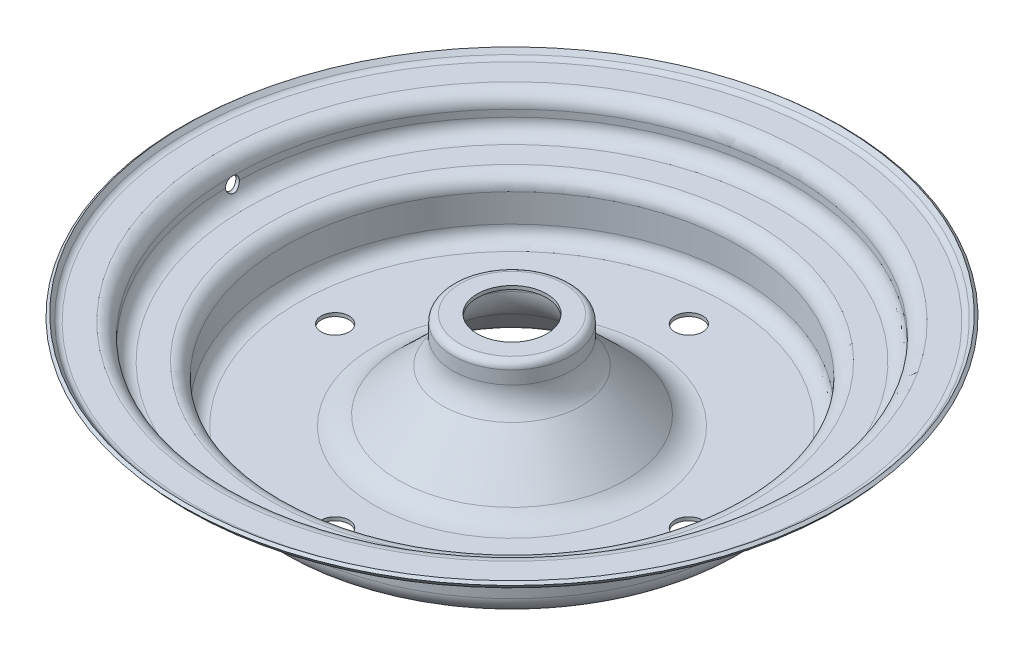
SolidWorks part; units mm, degrees
ref_plane "Ön Düzlem" through (0, 0, 0) normal (0, 0, 1) x (1, 0, 0)
ref_plane "Üst Düzlem" through (0, 0, 0) normal (0, 1, 0) x (1, 0, 0)
ref_plane "Sağ Düzlem" through (0, 0, 0) normal (1, 0, 0) x (0, 0, -1)
sketch "Çizim1" plane through (0, 0, 0) normal (0, 0, 1) x (1, 0, 0)
  line L0 (0, 39.6036) -> (0, -43.2542) construction
  line L1 (-94.234, 34.6808) -> (-93.2265, 33.4801)
  line L2 (-91.6944, 32.7656) -> (-84.627, 32.7656)
  line L3 (-80.627, 28.7656) -> (-80.627, 26.7656)
  line L4 (-76.627, 22.7656) -> (-69.627, 22.7656)
  line L5 (-65.627, 18.7656) -> (-65.627, 10.6808)
  line L6 (-61.627, 6.6808) -> (-39.6692, 6.6808)
  line L7 (-32.7202, 9.4897) -> (-20.051, 21.7325)
  line L8 (-17, 28.9235) -> (-17, 32.6808)
  line L9 (0, 0) -> (-159.2836, 0) construction
  line L10 (-15, 34.6808) -> (-10, 34.6808)
  line L11 (-95, 34.038) -> (-93.9925, 32.8373)
  line L12 (-91.6944, 31.7656) -> (-84.627, 31.7656)
  line L13 (-81.627, 28.7656) -> (-81.627, 26.7656)
  line L14 (-76.627, 21.7656) -> (-69.627, 21.7656)
  line L15 (-66.627, 18.7656) -> (-66.627, 10.6808)
  line L16 (-61.627, 5.6808) -> (-39.6692, 5.6808)
  line L17 (-32.0253, 8.7706) -> (-19.3561, 21.0134)
  line L18 (-16, 28.9235) -> (-16, 32.6808)
  line L19 (-15, 33.6808) -> (-11, 33.6808)
  line L20 (-94.234, 34.6808) -> (-95, 34.038)
  line L26 (-15, 33.6808) -> (-10, 33.6808) construction
  line L28 (-11, 33.6808) -> (-10, 33.6808)
  line L29 (-10, 33.6808) -> (-10, 34.6808)
  arc A0 (-65.627, 10.6808) -> (-61.627, 6.6808) centre (-61.627, 10.6808) ccw
  arc A1 (-69.627, 22.7656) -> (-65.627, 18.7656) centre (-69.627, 18.7656) cw
  arc A2 (-80.627, 26.7656) -> (-76.627, 22.7656) centre (-76.627, 26.7656) ccw
  arc A3 (-84.627, 32.7656) -> (-80.627, 28.7656) centre (-84.627, 28.7656) cw
  arc A4 (-39.6692, 6.6808) -> (-32.7202, 9.4897) centre (-39.6692, 16.6808) ccw
  arc A5 (-20.051, 21.7325) -> (-17, 28.9235) centre (-27, 28.9235) ccw
  arc A6 (-17, 32.6808) -> (-15, 34.6808) centre (-15, 32.6808) cw
  arc A7 (-93.2265, 33.4801) -> (-91.6944, 32.7656) centre (-91.6944, 34.7656) ccw
  arc A8 (-93.9925, 32.8373) -> (-91.6944, 31.7656) centre (-91.6944, 34.7656) ccw
  arc A9 (-84.627, 31.7656) -> (-81.627, 28.7656) centre (-84.627, 28.7656) cw
  arc A10 (-81.627, 26.7656) -> (-76.627, 21.7656) centre (-76.627, 26.7656) ccw
  arc A11 (-69.627, 21.7656) -> (-66.627, 18.7656) centre (-69.627, 18.7656) cw
  arc A12 (-66.627, 10.6808) -> (-61.627, 5.6808) centre (-61.627, 10.6808) ccw
  arc A13 (-39.6692, 5.6808) -> (-32.0253, 8.7706) centre (-39.6692, 16.6808) ccw
  arc A14 (-19.3561, 21.0134) -> (-16, 28.9235) centre (-27, 28.9235) ccw
  arc A15 (-16, 32.6808) -> (-15, 33.6808) centre (-15, 32.6808) cw
  point P30 (-65.627, 6.6808)
  point P33 (-65.627, 22.7656)
  point P36 (-80.627, 22.7656)
  point P39 (-80.627, 32.7656)
  point P42 (-35.627, 6.6808)
  point P45 (-17, 24.6808)
  point P48 (-17, 34.6808)
  point P51 (-92.627, 32.7656)
  dimension "D13" = 4
  dimension "D14" = 10
  dimension "D15" = 10
  dimension "D16" = 2
  dimension "D17" = 2
  dimension "D2" = 10
  dimension "D3" = 10
  dimension "D4" = 28
  dimension "D5" = 95
  dimension "D6" = 28
  dimension "D7" = 2.5
  dimension "D8" = 12
  dimension "D9" = 10
  dimension "D10" = 30
  dimension "D11" = 15
  dimension "D12" = 50
  dimension "D19" = 16
  dimension "D18" = 1
revolve "Döndür1" add sketch "Çizim1" angle 360 about L0 other way angle 360
sketch "Çizim2" plane through (0, 6.6808, 0) normal (0, 1, 0) x (1, 0, 0)
  circle A7 centre (0, 50.9725) radius 4
  circle A8 centre (50.9725, 0) radius 4
  circle A9 centre (0, -50.9725) radius 4
  circle A10 centre (-50.9725, 0) radius 4
  dimension "D2" = 8
  dimension "D3" = 8
  dimension "D4" = 8
  dimension "D5" = 8
extrude "Kes-Ekstrüzyon1" cut sketch "Çizim2" against normal blind 10
ref_plane "Düzlem1" through (-80.627, 0, 0) normal (1, 0, 0) x (0, 0, -1)
sketch "Çizim3" plane through (-80.627, 0, 0) normal (1, 0, 0) x (0, 0, -1)
  line L2 (-80.627, 28.7656) -> (80.627, 28.7656) construction
  circle A0 centre (0, 26.7656) radius 2
  dimension "D1" = 4
extrude "Kes-Ekstrüzyon4" cut sketch "Çizim3" against normal blind 11 and the other way blind 11
